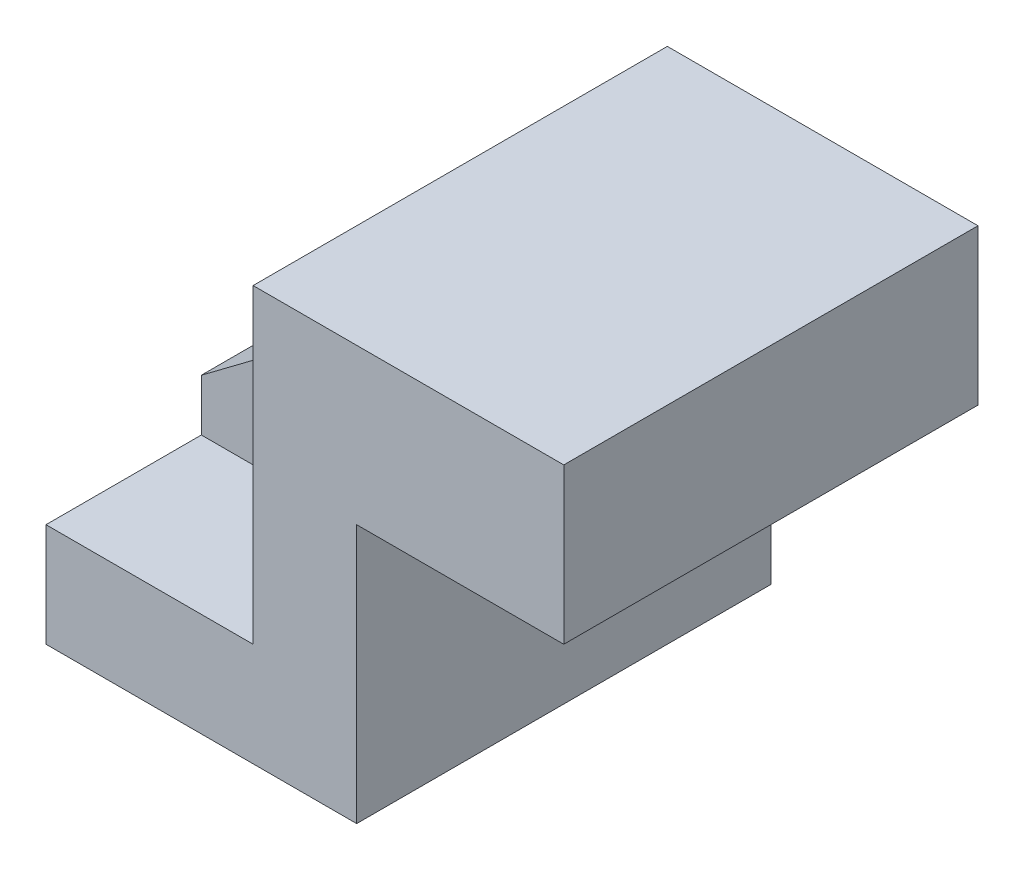
SolidWorks part; units mm, degrees
ref_plane "Front Plane" through (0, 0, 0) normal (0, 0, 1) x (1, 0, 0)
ref_plane "Top Plane" through (0, 0, 0) normal (0, 1, 0) x (1, 0, 0)
ref_plane "Right Plane" through (0, 0, 0) normal (1, 0, 0) x (0, 0, -1)
sketch "Sketch1" plane through (0, 0, 0) normal (0, 0, 1) x (1, 0, 0)
  line L0 (0, 0) -> (60, 0)
  line L1 (60, 0) -> (60, 50)
  line L2 (60, 50) -> (100, 50)
  line L3 (100, 50) -> (100, 80)
  line L4 (100, 80) -> (40, 80)
  line L5 (40, 80) -> (40, 20)
  line L6 (40, 20) -> (0, 20)
  line L7 (0, 20) -> (0, 0)
  line L8 (0, 20) -> (0, 30)
  line L9 (0, 30) -> (40, 60)
  dimension "D1" = 60
  dimension "D2" = 40
  dimension "D3" = 30
  dimension "D4" = 60
  dimension "D5" = 20
  dimension "D6" = 20
  dimension "D7" = 10
  dimension "D8" = 60
extrude "Boss-Extrude1" add sketch "Sketch1" along normal mid plane 80 contours L6 L7 L0 L1 L2 L3 L4 L5 region at (53.3333, 41.6667, 0)
extrude "Boss-Extrude2" add sketch "Sketch1<3>" along normal mid plane 20 contours L9 L8 L6 L5 region at (24, 34, 0)
sketch "Sketch1<3>" plane through (0, 0, 0) normal (0, 0, 1) x (1, 0, 0) same geometry as "Sketch1"
sketch "Sketch2" plane through (0, 0, 0) normal (1, 0, 0) x (0, 0, -1)
  line L0 (20, 0) -> (20, 10)
  line L1 (-40, 0) -> (40, 0) construction
  line L2 (20, 10) -> (-20, 10)
  line L3 (-20, 10) -> (-20, 0)
  line L4 (15, 80) -> (15, 60)
  line L5 (-40, 80) -> (40, 80) construction
  line L6 (15, 60) -> (-15, 60)
  line L7 (-15, 60) -> (-15, 80)
  dimension "D1" = 20
  dimension "D2" = 20
  dimension "D3" = 10
  dimension "D4" = 25
  dimension "D5" = 25
